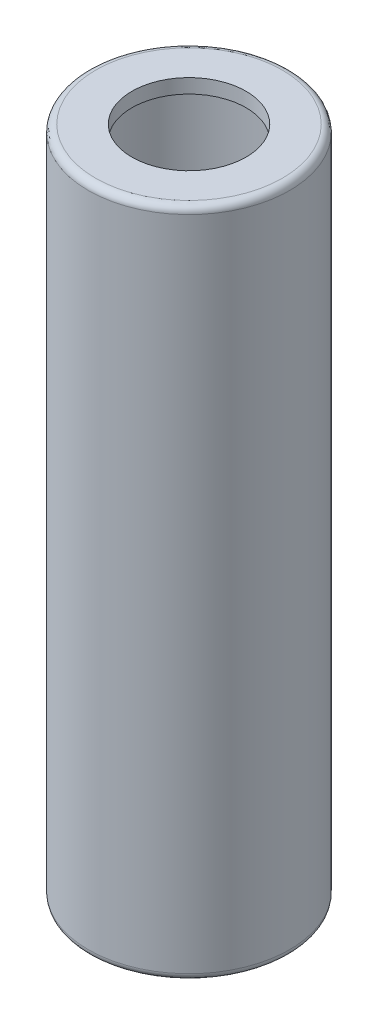
SolidWorks part; units mm, degrees
ref_plane "Спереди" through (0, 0, 0) normal (0, 0, 1) x (1, 0, 0)
ref_plane "Сверху" through (0, 0, 0) normal (0, 1, 0) x (1, 0, 0)
ref_plane "Справа" through (0, 0, 0) normal (1, 0, 0) x (0, 0, -1)
other "Configuration Table"
sketch "Эскиз1" plane through (0, 0, 0) normal (0, 1, 0) x (1, 0, 0)
  circle A0 centre (0, 0) radius 14.1
  dimension "D1" = 28.2
extrude "Бобышка-Вытянуть1" add sketch "Эскиз1" along normal blind 94
sketch "Эскиз2" plane through (0, 0, 0) normal (0, -1, 0) x (1, 0, 0)
  circle A0 centre (0, 0) radius 12.5
  dimension "D1" = 25
extrude "Вырез-Вытянуть1" cut sketch "Эскиз2" against normal blind 92
fillet "Скругление2" radius 1 1 edges at (0, 0, -12.5)
fillet "Скругление3" radius 1 1 edges at (0, 0, 14.1)
fillet "Скругление4" radius 1 1 edges at (0, 94, 14.1)
sketch "Эскиз3" plane through (0, 94, 0) normal (0, 1, 0) x (1, 0, 0)
  circle A0 centre (0, 0) radius 8
  dimension "D1" = 16
extrude "Вырез-Вытянуть2" cut sketch "Эскиз3" against normal blind 2
